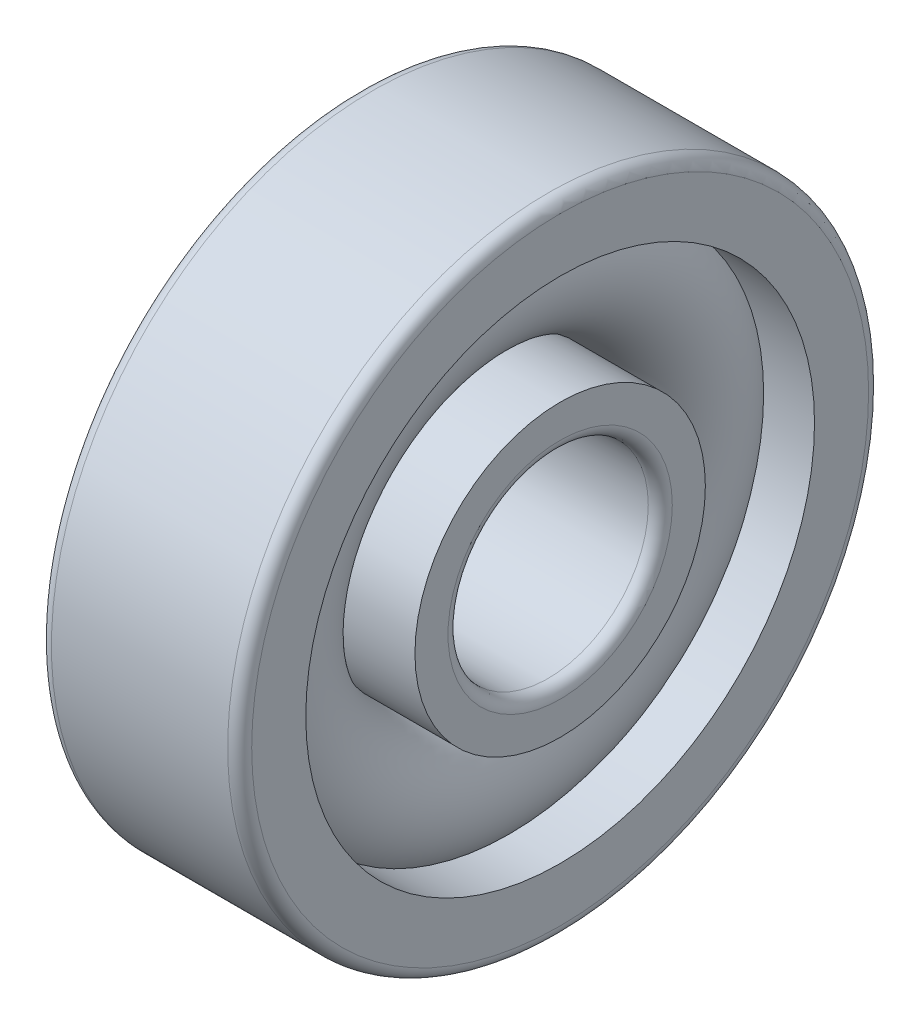
SolidWorks part; units mm, degrees
ref_plane "Plane1" through (0, 0, 0) normal (0, 0, 1) x (1, 0, 0)
ref_plane "Plane2" through (0, 0, 0) normal (0, 1, 0) x (1, 0, 0)
ref_plane "Plane3" through (0, 0, 0) normal (1, 0, 0) x (0, 0, -1)
sketch "Clipboard" plane through (0, 0, 0) normal (0, 0, 1) x (1, 0, 0)
  line L0 (-10, 0) -> (10, 0) construction
  line L1 (0, 0) -> (22.3471, -0.7804)
  line L2 (0, 0) -> (5.2468, 0.1832)
  line L3 (0, 0) -> (22.3471, -0.7804)
  line L4 (0, 0) -> (-22.3573, -0.3902)
  dimension "BallCLRad" = 5.25
sketch "CagSpiSke" plane through (0, 0, 0) normal (0, 0, 1) x (1, 0, 0)
  line L0 (0.4125, 4.975) -> (0.4125, 5.525)
  line L1 (0.4125, 5.525) -> (-0.4125, 5.525)
  line L2 (-0.4125, 5.525) -> (-0.4125, 4.975)
  line L3 (-0.4125, 4.975) -> (0.4125, 4.975)
  line L4 (-20.6375, 0) -> (20.6375, 0) construction
  line L5 (0, 0) -> (0, 23.7692) construction
  dimension "OD" = 11.05
  dimension "ID" = 9.95
revolve "CageSpine" add sketch "CagSpiSke" angle 0.001 about L4
ref_axis "Axis1" through (-50, 0, 0) along (1, 0, 0)
sketch "CagBalSke" plane through (0, 0, 0) normal (0, 0, 1) x (1, 0, 0)
  line L0 (-1.815, 5.25) -> (1.815, 5.25)
  line L1 (-1.905, 5.25) -> (1.905, 5.25) construction
  line L2 (-10, 0) -> (10, 0) construction
  line L3 (0, 0) -> (0, 24) construction
  arc A0 (1.815, 5.25) -> (-1.815, 5.25) centre (0, 5.25) cw
  dimension "BallCLRad" = 5.25
revolve "CageBall" [suppressed] add sketch "CagBalSke" angle 360 about L1 reverse direction yes
pattern_circular "CageBalls" [suppressed] count 2 every 180 about axis through (-50, 0, 0) along (1, 0, 0)
sketch "CagTrmODSke" plane through (0, 0, 0) normal (0, 0, 1) x (1, 0, 0)
  line L0 (1.816, 5.525) -> (1.816, 7.066)
  line L1 (1.816, 7.066) -> (-1.816, 7.066)
  line L2 (-1.816, 7.066) -> (-1.816, 5.525)
  line L3 (-1.816, 5.525) -> (1.816, 5.525)
  line L4 (-20.6375, 0) -> (20.6375, 0) construction
  line L5 (0, 0) -> (0, 25) construction
  dimension "Width" = 3.632
  dimension "ID" = 11.05
  dimension "OD" = 14.132
revolve "CageTrimOD" [suppressed] cut sketch "CagTrmODSke" angle 360 about L4 reverse direction yes
sketch "CagTrmIDSke" plane through (0, 0, 0) normal (0, 0, 1) x (1, 0, 0)
  line L0 (1.816, 3.436) -> (1.816, 4.975)
  line L1 (1.816, 4.975) -> (-1.816, 4.975)
  line L2 (-1.816, 4.975) -> (-1.816, 3.436)
  line L3 (-1.816, 3.436) -> (1.816, 3.436)
  line L4 (-20.6375, 0) -> (20.6375, 0) construction
  line L5 (0, 0) -> (0, 25) construction
  dimension "Width" = 3.632
  dimension "ID" = 6.872
  dimension "OD" = 9.95
revolve "CageTrimID" [suppressed] cut sketch "CagTrmIDSke" angle 360 about L4 reverse direction yes
sketch "BalSimSke" plane through (0, 0, 0) normal (0, 0, 1) x (1, 0, 0)
  line L0 (-10, 0) -> (10, 0) construction
  line L1 (-10, 5.25) -> (10, 5.25) construction
  line L2 (0, 0) -> (0, 23) construction
  circle A0 centre (0, 5.25) radius 1.65
  dimension "BallCLRad" = 5.25
  dimension "Ball_diameter" = 3.3
revolve "BallsSimplified" add sketch "BalSimSke" angle 360 about L0
sketch "BalDetSke" plane through (0, 0, 0) normal (0, 0, 1) x (1, 0, 0)
  line L0 (-1.65, 5.25) -> (1.65, 5.25)
  line L1 (-1.905, 5.25) -> (1.905, 5.25) construction
  line L2 (0, 0) -> (0, 25) construction
  arc A0 (1.65, 5.25) -> (-1.65, 5.25) centre (0, 5.25) cw
  dimension "BallCLRad" = 5.25
  dimension "Ball_diameter" = 3.3
revolve "BallDetailed" [suppressed] add sketch "BalDetSke" angle 360 about L1 reverse direction yes
sketch "InnRacSke" plane through (0, 0, 0) normal (0, 0, 1) x (1, 0, 0)
  line L0 (-1.1961, 4.15) -> (-2.5, 4.15)
  line L1 (-2.5, 4.15) -> (-2.5, 2.8)
  line L2 (-2.2, 2.5) -> (2.2, 2.5)
  line L3 (2.5, 2.8) -> (2.5, 3.625)
  line L4 (0, 3.625) -> (2.5, 3.625)
  line L5 (-20.6375, 0) -> (20.6375, 0) construction
  line L6 (0, 0) -> (0, 30) construction
  arc A0 (-2.5, 2.8) -> (-2.2, 2.5) centre (-2.2, 2.8) ccw
  arc A1 (2.2, 2.5) -> (2.5, 2.8) centre (2.2, 2.8) ccw
  arc A2 (0, 3.625) -> (-1.1961, 4.15) centre (0, 5.25) cw
  dimension "BallCLRad" = 5.25
  dimension "Fillet_radius" = 0.3
  dimension "Ball_diameter" = 3.25
  dimension "ID" = 5
  dimension "OD" = 8.3
  dimension "Width" = 5
revolve "InnerRace" add sketch "InnRacSke" angle 360 about L5 reverse direction yes
sketch "OutRacSke" plane through (0, 0, 0) normal (0, 0, 1) x (1, 0, 0)
  line L0 (0, 6.875) -> (-2.5, 6.875)
  line L1 (-2.5, 6.875) -> (-2.5, 7.7)
  line L2 (-2.2, 8) -> (2.2, 8)
  line L3 (2.5, 7.7) -> (2.5, 6.35)
  line L4 (2.5, 6.35) -> (1.1961, 6.35)
  line L5 (-20.6375, 0) -> (20.6375, 0) construction
  line L6 (0, 0) -> (0, 30) construction
  arc A0 (-2.5, 7.7) -> (-2.2, 8) centre (-2.2, 7.7) cw
  arc A1 (2.2, 8) -> (2.5, 7.7) centre (2.2, 7.7) cw
  arc A2 (1.1961, 6.35) -> (0, 6.875) centre (0, 5.25) ccw
  dimension "BallCLRad" = 5.25
  dimension "Fillet_radius" = 0.3
  dimension "Ball_diameter" = 3.25
  dimension "Width" = 5
revolve "OuterRace" add sketch "OutRacSke" angle 360 about L5 reverse direction yes
pattern_circular "BallsDetailed" [suppressed] count 2 every 180 about axis through (-50, 0, 0) along (1, 0, 0)
equation "\"BallCLRad@Clipboard\" = ( \"OD@OutRacSke\" + \"ID@InnRacSke\" ) / 4"
equation "\"BallCLRad@BalSimSke\" = \"BallCLRad@Clipboard\""
equation "\"BallCLRad@BalDetSke\" = \"BallCLRad@Clipboard\""
equation "\"BallCLRad@InnRacSke\" = \"BallCLRad@Clipboard\""
equation "\"BallCLRad@OutRacSke\" = \"BallCLRad@Clipboard\""
equation "\"Ball_diameter@InnRacSke\" = \"Ball_diameter@BalDetSke\" - 0.05"
equation "\"Ball_diameter@OutRacSke\" = \"Ball_diameter@BalDetSke\" - 0.05"
equation "\"Ball_diameter@BalSimSke\" = \"Ball_diameter@BalDetSke\""
equation "\"Width@OutRacSke\" = \"Width@InnRacSke\""
equation "\"Fillet_radius@OutRacSke\" = \"Fillet_radius@InnRacSke\""
equation "\"Max_count@Clipboard\" = int( 3.14159265 / atn(( \"Ball_diameter@BalDetSke\" / 2) / sqr( \"BallCLRad@Clipboard\"  *  \"BallCLRad@Clipboard\" - ( \"Ball_diameter@BalDetSke\" / 2) *  ( \"Ball_diameter@BalDetSke\" / 2))))"
equation "\"Max_count@Clipboard\" = ((sgn( \"Max_count@Clipboard\" - \"Count@Clipboard\" )-1)*( \"Max_count@Clipboard\" - \"Count@Clipboard\" ))/-2+ \"Count@Clipboard\""
equation "\"Count@BallsDetailed\" = int( \"Show_count@Clipboard\" ) "
equation "\"Count@BallsDetailed\" = ((sgn( \"Count@BallsDetailed\" - \"Max_count@Clipboard\" )-1)*( \"Count@BallsDetailed\" - \"Max_count@Clipboard\" ))/-2+ \"Max_count@Clipboard\""
equation "\"Count@BallsDetailed\" = ((sgn( \"Count@BallsDetailed\" - \"Min_count@Clipboard\" )+1)*( \"Count@BallsDetailed\" - \"Min_count@Clipboard\"))/2 +\"Min_count@Clipboard\""
equation "\"Angle@BallsDetailed\" = 360.0 / \"Max_count@Clipboard\""
equation "\"BallCLRad@CagBalSke\" = \"BallCLRad@Clipboard\""
equation "\"Count@CageBalls\" = \"Count@BallsDetailed\""
equation "\"Angle@CageBalls\" = \"Angle@BallsDetailed\""
equation "\"Angle@CageSpine\" =  \"Angle@CageBalls\" * ( \"Count@CageBalls\" -1 + int( \"Count@CageBalls\" / \"Max_count@Clipboard\" ) )  + 0.001 -  int( \"Count@CageBalls\" / \"Max_count@Clipboard\" ) * 0.001"
equation "\"Angle@CageSpine\" =  \"Angle@CageSpine\" * int( \"Min_count@Clipboard\" / 2) + int(1 / \"Min_count@Clipboard\")  * 0.001"
equation "\"CageWallOD@CagBalSke\" =  \"Ball_diameter@BalDetSke\" * 1.1"
equation "\"Thickness@CagSpiSke\" =  \"Ball_diameter@BalDetSke\" * 0.25"
equation "\"OD@CagTrmODSke\" = \"BallCLRad@Clipboard\" * 2 + \"CageWallOD@CagBalSke\" + 0.002"
equation "\"ID@CagTrmODSke\" = \"BallCLRad@Clipboard\" * 2 + \"Ball_diameter@BalDetSke\" / 6"
equation "\"OD@CagTrmIDSke\" = \"BallCLRad@Clipboard\" * 2 - \"Ball_diameter@BalDetSke\" / 6"
equation "\"ID@CagTrmIDSke\" = \"BallCLRad@Clipboard\" * 2 - \"CageWallOD@CagBalSke\" + 0.002"
equation "\"OD@CagSpiSke\" = \"ID@CagTrmODSke\""
equation "\"ID@CagSpiSke\" = \"OD@CagTrmIDSke\""
equation "\"Width@CagTrmODSke\" = \"CageWallOD@CagBalSke\" + 0.002"
equation "\"Width@CagTrmIDSke\" = \"CageWallOD@CagBalSke\" + 0.002"
